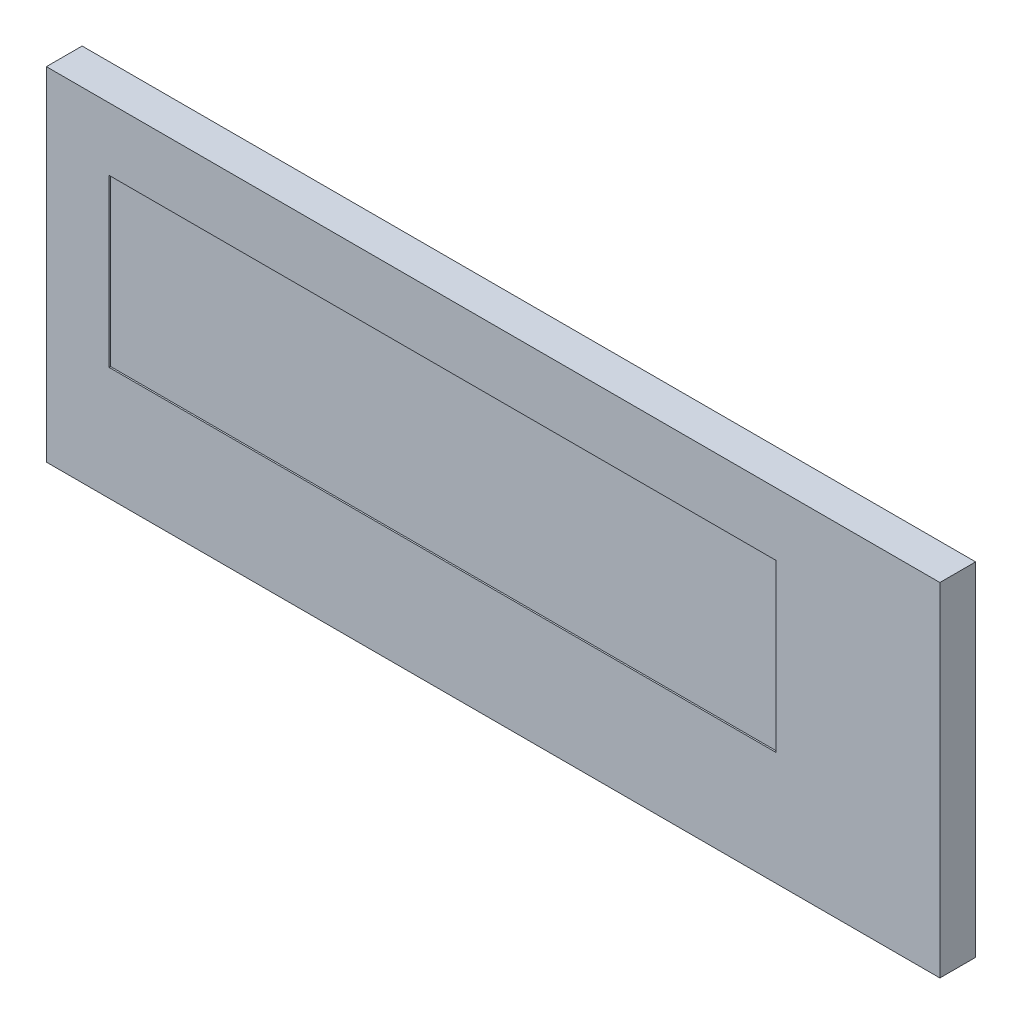
SolidWorks part; units mm, degrees
ref_plane "前视基准面" through (0, 0, 0) normal (0, 0, 1) x (1, 0, 0)
ref_plane "上视基准面" through (0, 0, 0) normal (0, 1, 0) x (1, 0, 0)
ref_plane "右视基准面" through (0, 0, 0) normal (1, 0, 0) x (0, 0, -1)
sketch "草图1" plane through (0, 0, 0) normal (0, 0, 1) x (1, 0, 0)
  line L1 (-11.192, 2.792) -> (11.192, 2.792)
  line L2 (-11.192, 2.792) -> (-11.192, -2.792)
  line L3 (-11.192, -2.792) -> (11.192, -2.792)
  line L4 (11.192, 2.792) -> (11.192, -2.792)
  line L5 (-11.192, 2.792) -> (11.192, -2.792) construction
  line L6 (-11.192, -2.792) -> (11.192, 2.792) construction
  line L7 (-12.95, 4.4) -> (12.95, 4.4)
  line L8 (-12.95, 4.4) -> (-12.95, -4.4)
  line L9 (-12.95, -4.4) -> (12.95, -4.4)
  line L10 (12.95, 4.4) -> (12.95, -4.4)
  line L11 (-12.95, 4.4) -> (12.95, -4.4) construction
  line L12 (-12.95, -4.4) -> (12.95, 4.4) construction
  line L13 (-13.3, 4.9) -> (16.7, 4.9)
  line L14 (-13.3, 4.9) -> (-13.3, -6.6)
  line L15 (-13.3, -6.6) -> (16.7, -6.6)
  line L16 (16.7, 4.9) -> (16.7, -6.6)
  line L17 (-13.3, 4.9) -> (16.7, -6.6) construction
  line L18 (-13.3, -6.6) -> (16.7, 4.9) construction
  point P0 (0, 0)
  point P6 (0, 0)
  point P11 (0, -7.9237)
  point P12 (1.7, -0.85)
  point P17 (0, 0)
  point P18 (0.7924, -5.1737)
  point P19 (0.839, -0.85)
  point P21 (27.3602, 5.3136)
  point P22 (15.1699, 4.6614)
  dimension "D1" = 22.384
  dimension "D2" = 5.584
  dimension "D3" = 25.9
  dimension "D4" = 8.8
  dimension "D5" = 11.5
  dimension "D6" = 30
  dimension "D7" = 0.5
  dimension "D8" = 0.35
extrude "凸台-拉伸2" add sketch "草图1" along normal blind 1.2 contours L16 L13 L14 L15 L7 L10 L9 L8 | L10 L7 L8 L9 L1 L4 L3 L2 region at (0, 4.1265, 0) region at (1.7, 4.5787, 0)
extrude "凸台-拉伸4" add sketch "草图1<6>" along normal blind 1.15 contours L4 L1 L2 L3 region at (0, 0, 0)
sketch "草图1<6>" plane through (0, 0, 0) normal (0, 0, 1) x (1, 0, 0) same geometry as "草图1"
